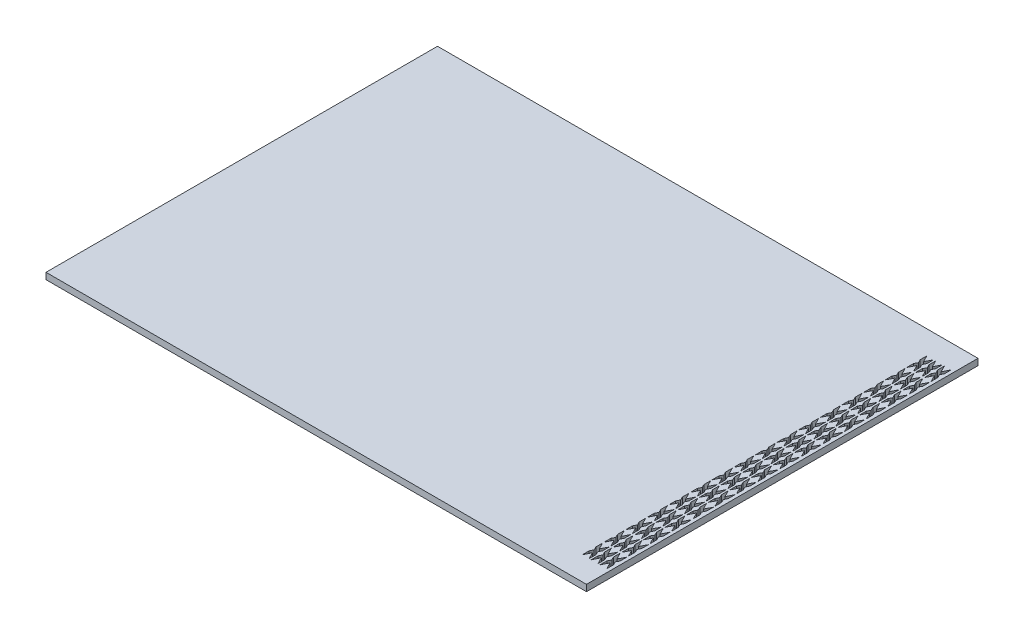
SolidWorks part; units mm, degrees
ref_plane "Front Plane" through (0, 0, 0) normal (0, 0, 1) x (1, 0, 0)
ref_plane "Top Plane" through (0, 0, 0) normal (0, 1, 0) x (1, 0, 0)
ref_plane "Right Plane" through (0, 0, 0) normal (1, 0, 0) x (0, 0, -1)
sketch "Sketch1" plane through (0, 0, 0) normal (0, 1, 0) x (1, 0, 0)
  line L1 (-66.3921, 26.7316) -> (136.8079, 26.7316)
  line L2 (-66.3921, 26.7316) -> (-66.3921, -120.4614)
  line L3 (-66.3921, -120.4614) -> (136.8079, -120.4614)
  line L4 (136.8079, 26.7316) -> (136.8079, -120.4614)
  dimension "D1" = 203.2
  dimension "D2" = 147.193
extrude "Boss-Extrude1" add sketch "Sketch1" along normal blind 2.413
sketch "Sketch2" plane through (0, 2.413, 0) normal (0, 1, 0) x (0, 0, -1)
  line L0 (-111.5714, -132.9979) -> (-109.0514, -134.2679)
  line L1 (-111.5714, -132.9979) -> (-109.0314, -132.9979)
  line L2 (-106.5314, -135.5379) -> (-103.9914, -135.5379)
  line L3 (-109.0314, -132.9979) -> (-107.7814, -133.6279)
  line L4 (-106.5314, -132.9979) -> (-107.7814, -133.6279)
  line L5 (-106.5314, -132.9979) -> (-103.9914, -132.9979)
  line L6 (-111.5714, -135.5379) -> (-109.0314, -135.5379)
  line L7 (-103.9914, -132.9979) -> (-106.5114, -134.2679)
  line L8 (-120.4614, -136.8079) -> (26.7316, -136.8079) construction
  line L9 (-120.4614, 66.3921) -> (-120.4614, -136.8079) construction
  line L10 (-107.7814, -134.908) -> (-106.5314, -135.5379)
  line L11 (-106.5114, -134.2679) -> (-103.9914, -135.5379)
  line L12 (-109.0514, -134.2679) -> (-111.5714, -135.5379)
  line L13 (-107.7814, -134.908) -> (-109.0314, -135.5379)
  point P0 (0, 0)
  point P6 (-102.5982, -422.0181)
  point P11 (-102.5982, -422.0181)
  point P12 (-102.5982, -422.0181)
  point P13 (-102.5982, -422.0181)
  point P14 (-78.466, -336.8147)
  point P15 (-105.5458, -132.3447)
  point P20 (-160.1313, -245.0701)
  dimension "D1" = 2.54
  dimension "D2" = 2.5
  dimension "D3" = 2.54
  dimension "D4" = 1.27
  dimension "D5" = 8.89
extrude "Cut-Extrude1" cut sketch "Sketch2" against normal blind 2.794
pattern_linear "LPattern1" count 16 spacing 8.128 along (0, 0, -1) count 3 spacing 3.302 along (-1, 0, 0) of "Cut-Extrude1"
